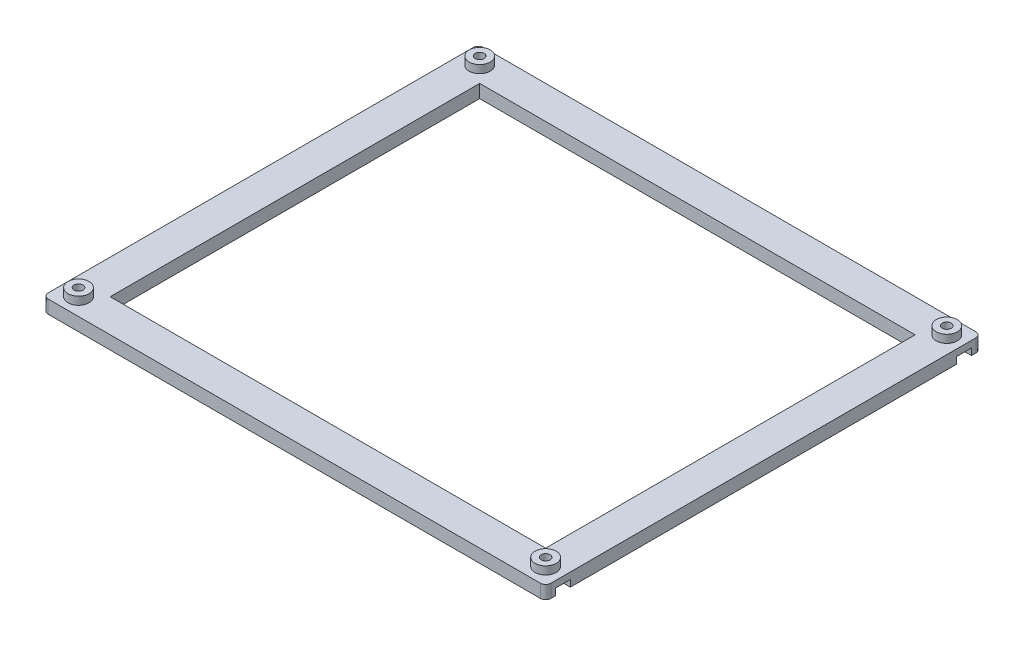
SolidWorks part; units mm, degrees
ref_plane "Front Plane" through (0, 0, 0) normal (0, 0, 1) x (1, 0, 0)
ref_plane "Top Plane" through (0, 0, 0) normal (0, 1, 0) x (1, 0, 0)
ref_plane "Right Plane" through (0, 0, 0) normal (1, 0, 0) x (0, 0, -1)
sketch "Sketch2" plane through (0, 0, 0) normal (0, 1, 0) x (1, 0, 0)
  line L1 (-92.5, -80) -> (92.5, -80)
  line L2 (-92.5, -80) -> (-92.5, 80)
  line L3 (-92.5, 80) -> (92.5, 80)
  line L4 (92.5, -80) -> (92.5, 80)
  line L5 (0, 80) -> (0, -80) construction
  line L6 (-92.5, 0) -> (92.5, 0) construction
  line L7 (-82.5, -70) -> (82.5, -70)
  line L8 (-82.5, -70) -> (-82.5, 70)
  line L9 (-82.5, 70) -> (82.5, 70)
  line L10 (82.5, -70) -> (82.5, 70)
  line L11 (0, 70) -> (0, -70) construction
  line L12 (-82.5, 0) -> (82.5, 0) construction
  line L13 (90.1454, 78.85) -> (91.7909, 76)
  line L14 (-91.7909, 76) -> (-90.1454, 73.15)
  line L15 (-90.1454, 73.15) -> (-86.8546, 73.15)
  line L16 (-86.8546, 73.15) -> (-85.2091, 76)
  line L17 (-85.2091, 76) -> (-86.8546, 78.85)
  line L18 (-86.8546, 78.85) -> (-90.1454, 78.85)
  line L19 (-90.1454, 78.85) -> (-91.7909, 76)
  line L20 (86.8546, 78.85) -> (90.1454, 78.85)
  line L21 (85.2091, 76) -> (86.8546, 78.85)
  line L22 (86.8546, 73.15) -> (85.2091, 76)
  line L23 (90.1454, 73.15) -> (86.8546, 73.15)
  line L24 (91.7909, 76) -> (90.1454, 73.15)
  line L25 (86.8546, -78.85) -> (90.1454, -78.85)
  line L26 (85.2091, -76) -> (86.8546, -78.85)
  line L27 (86.8546, -73.15) -> (85.2091, -76)
  line L28 (90.1454, -73.15) -> (86.8546, -73.15)
  line L29 (91.7909, -76) -> (90.1454, -73.15)
  line L30 (90.1454, -78.85) -> (91.7909, -76)
  line L31 (-90.1454, -78.85) -> (-91.7909, -76)
  line L32 (-86.8546, -78.85) -> (-90.1454, -78.85)
  line L33 (-85.2091, -76) -> (-86.8546, -78.85)
  line L34 (-86.8546, -73.15) -> (-85.2091, -76)
  line L35 (-90.1454, -73.15) -> (-86.8546, -73.15)
  line L36 (-91.7909, -76) -> (-90.1454, -73.15)
  line L37 (-90.1454, 78.85) -> (-92.5, 78.85)
  line L38 (-90.1454, 73.15) -> (-92.5, 73.15)
  line L39 (90.1454, 73.15) -> (92.5, 73.15)
  line L40 (90.1454, 78.85) -> (92.5, 78.85)
  line L41 (90.1454, -73.15) -> (95, -73.15)
  line L42 (90.1454, -78.85) -> (95, -78.85)
  line L43 (-86.8546, -73.15) -> (-95.5, -73.15)
  line L44 (-90.1454, -78.85) -> (-95.5, -78.85)
  line L45 (95, 82.5) -> (95, -82.5)
  line L46 (-95.5, 82.5) -> (-95.5, -82.5)
  line L47 (-95.5, -82.5) -> (95, -82.5)
  line L48 (95, -82.5) -> (95, 82.5)
  line L49 (-95.5, -82.5) -> (-95.5, 82.5)
  line L50 (90.1454, 78.85) -> (95, 78.85)
  line L51 (90.1454, 73.15) -> (95, 73.15)
  line L52 (-90.1454, 78.85) -> (-95.5, 78.85)
  line L53 (-86.8546, 73.15) -> (-95.5, 73.15)
  line L54 (-95.5, 82.5) -> (95, 82.5)
  circle A0 centre (-88.5, 76) radius 1.7
  circle A1 centre (88.5, 76) radius 1.7
  circle A2 centre (88.5, -76) radius 1.7
  circle A3 centre (-88.5, -76) radius 1.7
  circle A4 centre (-88.5, 76) radius 2.85 construction
  circle A5 centre (-88.5, -76) radius 4
  circle A6 centre (-88.5, 76) radius 4
  circle A7 centre (88.5, 76) radius 4
  circle A8 centre (88.5, -76) radius 4
  point P0 (0, 0)
  point P4 (0, 0)
  dimension "D5" = 3.4
  dimension "D1" = 160
  dimension "D2" = 185
  dimension "D3" = 10
  dimension "D4" = 10
  dimension "D6" = 5.7
  dimension "D7" = 2.5
  dimension "D8" = 2.5
  dimension "D9" = 3
  dimension "D10" = 90
  dimension "D11" = 4
  dimension "D12" = 4
extrude "Boss-Extrude1" add sketch "Sketch2" against normal blind 5 contours L46 L47 L45 L42 L4 L1 L2 L44 | A5 L44 L2 L1 | A5 L43 L35 L34 L33 L32 L44 | A8 L41 L4 L51 A7 L3 A6 L53 L2 L43 A5 L1 L10 L7 L8 L9 | L2 L53 L46 L43 | A6 L3 L2 L52 | A6 L37 L18 L17 L16 L15 L38 | A7 L50 L4 L3 | L40 A7 L39 L23 L22 L21 L20 | L54 L46 L52 L2 L3 L4 L50 L45 | L51 L4 L41 L45 | A8 L42 L25 L26 L27 L28 L41 | A8 L1 L4 L42 region at (-91.3636, 0, 79.5267) region at (-0.3602, 0, 81.2261) region at (-85.4986, 0, 79.0014) region at (-89.9768, 0, 79.6042) region at (91.3636, 0, 79.5267) region at (84.8958, 0, 74.5232) region at (-94, 0, 0) region at (93.75, 0, 0) region at (-90.7261, 0, -73.045) region at (-0.3602, 0, -81.2261) region at (84.8958, 0, -74.5232) region at (-91.3636, 0, -79.5267) region at (91.3636, 0, -79.5267)
extrude "Boss-Extrude2" add sketch "Sketch2<3>" against normal blind 2.5 contours L18 L19 L14 L15 L16 L17 A0 | L36 L31 L32 L33 L34 L35 A3 | L25 L30 L29 L28 L27 L26 A2 | L24 L13 L20 L21 L22 L23 A1 | L40 L13 L24 L39 L4 | L30 L42 L4 L41 L29 | L44 L31 L36 L43 L2 | L38 L14 L19 L37 L2 | L43 L46 L44 L2 | L42 L48 L41 L4 | L4 L51 L48 L50 | A6 L52 L2 | L53 L2 L52 L49 | A6 L2 L53 | A5 L43 L2 | A5 L2 L44 | A8 L4 L41 | A8 L42 L4 | A7 L4 L50 | A7 L51 L4 region at (-94, 0, 76) region at (-92.1535, 0, 78.1605) region at (-92.1327, 0, 77.5211) region at (-92.1535, 0, 73.8395) region at (92.1327, 0, 74.4789) region at (92.1535, 0, 73.8395) region at (92.1535, 0, 78.1605) region at (-90.8928, 0, 77.3815) region at (93.75, 0, 76) region at (90.8928, 0, 74.6185) region at (-94, 0, -76) region at (-92.1535, 0, -73.8395) region at (92.1535, 0, -73.8395) region at (93.75, 0, -76) region at (-92.1535, 0, -78.1605) region at (-92.1327, 0, -77.5211) region at (92.1535, 0, -78.1605) region at (92.1327, 0, -74.4789) region at (-90.8928, 0, -74.6185) region at (88.5, 0, -73.2371)
sketch "Sketch2<3>" plane through (0, 0, 0) normal (0, 1, 0) x (1, 0, 0) same geometry as "Sketch2"
extrude "Boss-Extrude3" add sketch "Sketch2<5>" along normal blind 3 contours L4 L39 L23 L22 L21 L20 L40 L3 | L24 L13 L20 L21 L22 L23 A1 | L40 L13 L24 L39 L4 | L3 L2 L37 L18 L17 L16 L15 L38 | L38 L14 L19 L37 L2 | L18 L19 L14 L15 L16 L17 A0 | L2 L43 L35 L34 L33 L32 L44 L1 | L36 L31 L32 L33 L34 L35 A3 | L44 L31 L36 L43 L2 | L1 L4 L42 L25 L26 L27 L28 L41 | L30 L42 L4 L41 L29 | L25 L30 L29 L28 L27 L26 A2 region at (-89.9768, 0, 79.6042) region at (84.8958, 0, 74.5232) region at (-92.1327, 0, 77.5211) region at (92.1327, 0, 74.4789) region at (-90.8928, 0, 77.3815) region at (90.8928, 0, 74.6185) region at (-92.1327, 0, -77.5211) region at (-90.7261, 0, -73.045) region at (92.1327, 0, -74.4789) region at (84.8958, 0, -74.5232) region at (-90.8928, 0, -74.6185) region at (88.5, 0, -73.2371)
sketch "Sketch2<5>" plane through (0, 0, 0) normal (0, 1, 0) x (1, 0, 0) same geometry as "Sketch2"
fillet "Fillet1" radius 2 4 edges at (95, -2.5, -82.5) (-95.5, -2.5, -82.5) (-95.5, -2.5, 82.5) (95, -2.5, 82.5)
